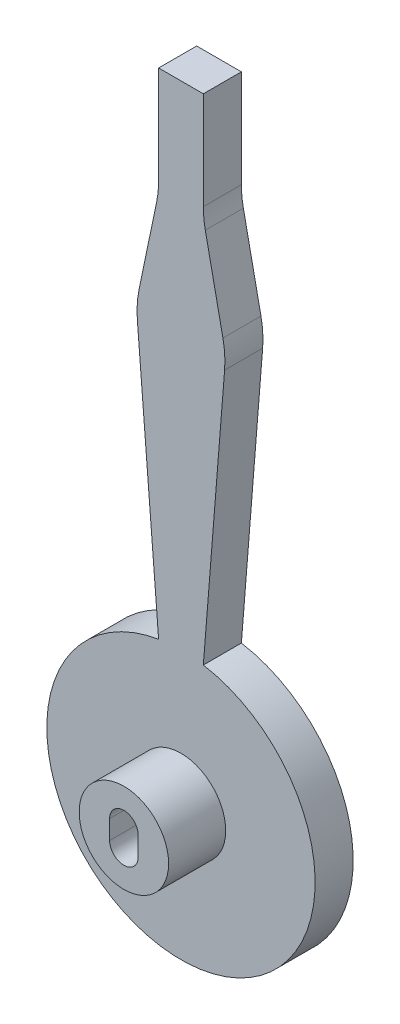
SolidWorks part; units mm, degrees
ref_plane "Front Plane" through (0, 0, 0) normal (0, 0, 1) x (1, 0, 0)
ref_plane "Top Plane" through (0, 0, 0) normal (0, 1, 0) x (1, 0, 0)
ref_plane "Right Plane" through (0, 0, 0) normal (1, 0, 0) x (0, 0, -1)
sketch "Sketch1" plane through (0, 0, 0) normal (0, 0, 1) x (1, 0, 0)
  line L0 (0, 0) -> (4.7, 0)
  line L1 (0, -14.1) -> (0, 65.9)
  line L2 (-4.7, 13.2936) -> (-4.7, 43.2936)
  line L3 (4.7, 13.2936) -> (4.7, 43.2936)
  line L4 (-4.4082, 44.6972) -> (-2.5594, 53.5898)
  line L5 (-2.35, 55.6253) -> (-2.35, 65.9)
  line L6 (-2.35, 65.9) -> (2.35, 65.9)
  line L7 (2.35, 65.9) -> (2.35, 55.6253)
  line L8 (2.5594, 53.5898) -> (4.4082, 44.6972)
  line L9 (-2.35, 13.9028) -> (-4.5857, 41.8646)
  line L10 (2.35, 13.9028) -> (4.5857, 41.8646)
  circle A0 centre (0, 0) radius 4.7
  circle A1 centre (0, 0) radius 14.1
  arc A2 (4.4082, 44.6972) -> (4.5857, 41.8646) centre (-5.3824, 42.6616) cw
  arc A3 (-4.4082, 44.6972) -> (-4.5857, 41.8646) centre (5.3824, 42.6616) ccw
  arc A4 (-2.35, 55.6253) -> (-2.5594, 53.5898) centre (-12.35, 55.6253) cw
  arc A5 (2.35, 55.6253) -> (2.5594, 53.5898) centre (12.35, 55.6253) ccw
  point P7 (-4.7, 0)
  point P8 (14.1, 0)
  point P9 (-14.1, 0)
  point P10 (4.7, 13.2936)
  point P11 (-4.7, 13.2936)
  point P16 (2.35, 54.5968)
  point P17 (-2.35, 54.5968)
  point P22 (-2.35, 13.9028)
  point P23 (2.35, 13.9028)
  point P34 (-2.35, 54.5968)
  point P37 (2.35, 54.5968)
  dimension "D3" = 28.2
  dimension "D8" = 10
  dimension "D9" = 10
  dimension "D10" = 10
  dimension "D11" = 10
  dimension "D1" = 4.7
  dimension "D2" = 80
  dimension "D4" = 30
  dimension "D5" = 30
  dimension "D6" = 13.2936
  dimension "D7" = 13.2936
  dimension "D12" = 4.7
  dimension "D13" = 27.9618
  dimension "D14" = 27.9618
  dimension "D15" = 10.2747
  dimension "D16" = 10.2747
  dimension "D17" = 23.49
extrude "Boss-Extrude1" add sketch "Sketch1" along normal blind 4 contours A1 L1 A0 | L1 A1 A0 | L5 A4 L4 A3 L9 A1 L1 L6 | A5 L7 L6 L1 A1 L10 A2 L8 region at (6.4829, 0, 0) region at (-6.4829, 0, 0) region at (-1.7258, 39.2066, 0) region at (1.7258, 39.2066, 0)
extrude "Boss-Extrude2" add sketch "Sketch1<3>" along normal blind 10 contours L1 A0 L0 | L0 A0 L1 | L1 A0 region at (1.9947, 1.9947, 0) region at (1.9947, -1.9947, 0) region at (-1.9947, 0, 0)
sketch "Sketch1<3>" plane through (0, 0, 0) normal (0, 0, 1) x (1, 0, 0) same geometry as "Sketch1"
sketch "Sketch2" plane through (0, 0, 10) normal (0, 0, 1) x (1, 0, 0)
  line L0 (0, 1) -> (0, -1) construction
  line L1 (1.5, 1) -> (1.5, -1)
  line L2 (-1.5, 1) -> (-1.5, -1)
  arc A0 (1.5, 1) -> (-1.5, 1) centre (0, 1) ccw
  arc A1 (-1.5, -1) -> (1.5, -1) centre (0, -1) ccw
  point P3 (0, 0)
  point P8 (0, 2.5)
  point P9 (0, -2.5)
  dimension "D1" = 5
  dimension "D2" = 3
extrude "Cut-Extrude1" cut sketch "Sketch2" against normal blind 3
